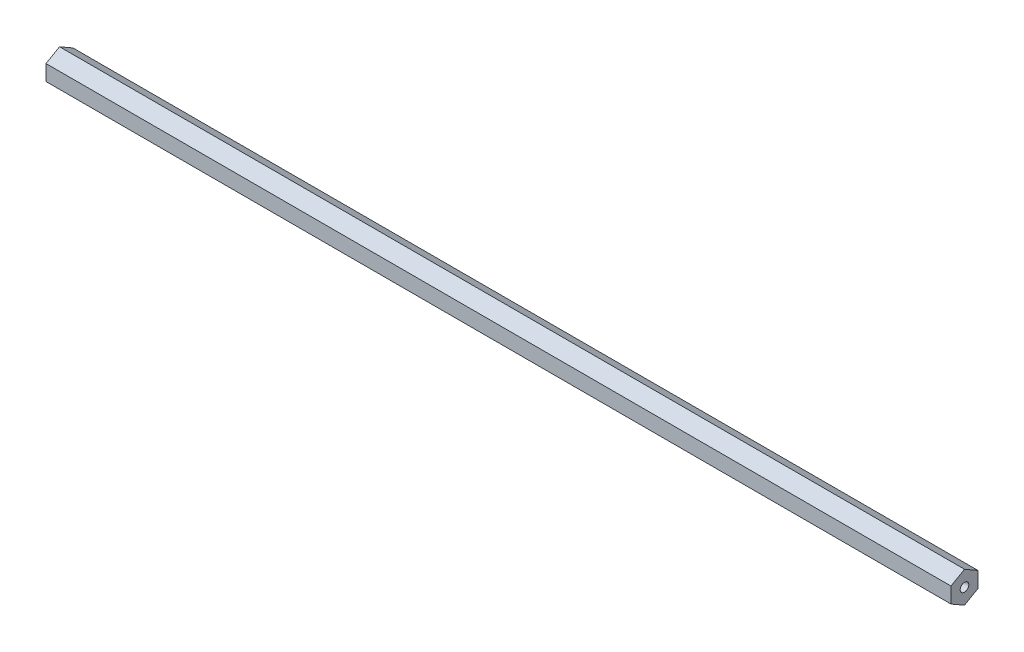
SolidWorks part; units mm, degrees
material "7075-T6 (SN)"
ref_plane "Front Plane" through (0, 0, 0) normal (0, 0, 1) x (1, 0, 0)
ref_plane "Top Plane" through (0, 0, 0) normal (0, 1, 0) x (1, 0, 0)
ref_plane "Right Plane" through (0, 0, 0) normal (1, 0, 0) x (0, 0, -1)
sketch "Sketch1" plane through (0, 0, 0) normal (1, 0, 0) x (0, 0, -1)
  line L1 (0, 7.3323) -> (-6.35, 3.6662)
  line L2 (-6.35, 3.6662) -> (-6.35, -3.6662)
  line L3 (-6.35, -3.6662) -> (0, -7.3323)
  line L4 (0, -7.3323) -> (6.35, -3.6662)
  line L5 (6.35, -3.6662) -> (6.35, 3.6662)
  line L6 (6.35, 3.6662) -> (0, 7.3323)
  circle A2 centre (0, 0) radius 6.35 construction
  dimension "D2" = 12.7
extrude "Boss-Extrude1" add sketch "Sketch1" along normal mid plane 425.45 contours L5 L6 L1 L2 L3 L4 region at (0, 0, 0)
sketch "Sketch3" plane through (-200.8187, 0, 0) normal (-1, 0, 0) x (0, 0, 1)
  circle A0 centre (0, 0) radius 6.35
  dimension "D1" = 12.7
hole_wizard "#10-32 Tapped Hole1" positions "3DSketch1" profile "Sketch4" tap size "#10-32" standard "ANSI Inch"
sketch3d "3DSketch1"
  point P9 (212.725, 0, 0)
  point P27 (-212.725, 0, 0)
sketch "Sketch4" plane through (212.725, 0, 0) normal (0, 1, 0) x (0, 0, -1)
  line L0 (0, 0) -> (0, 17.5608)
  line L1 (0, 17.5608) -> (2.0193, 16.3474)
  line L2 (2.0193, 16.3474) -> (2.0193, 0)
  line L5 (2.0193, 0) -> (0, 0)
  line L10 (0, 17.5608) -> (-2.0193, 16.3474) construction
  line L11 (0, -6.35) -> (0, 107.95) construction
  dimension "Tap Drill Dia." = 4.0386
  dimension "Tap Drill Depth" = 16.3474
  dimension "Drill Angle" = 118
cosmetic thread "Hole Thread2"
cosmetic thread "Hole Thread3"
